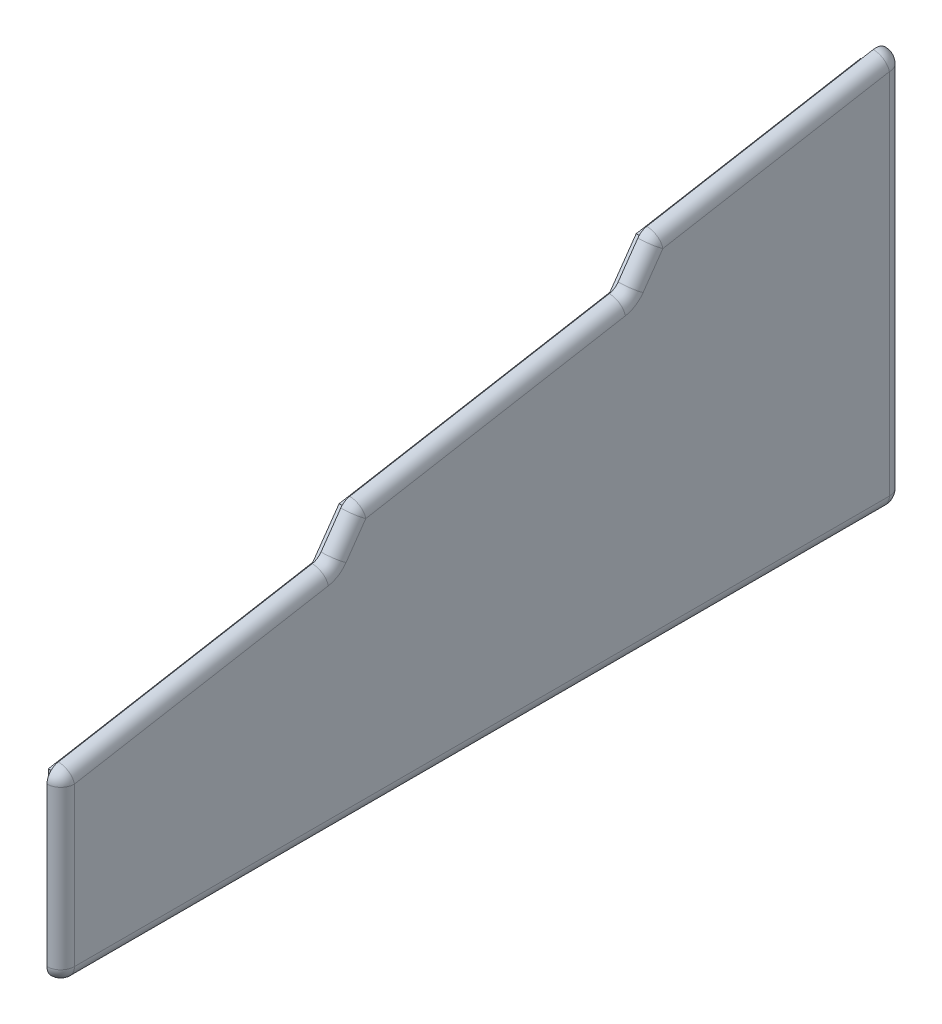
SolidWorks part; units mm, degrees
ref_plane "Front Plane" through (0, 0, 0) normal (0, 0, 1) x (1, 0, 0)
ref_plane "Top Plane" through (0, 0, 0) normal (0, 1, 0) x (1, 0, 0)
ref_plane "Right Plane" through (0, 0, 0) normal (1, 0, 0) x (0, 0, -1)
sketch "Sketch1" plane through (-376.4232, 0, 0) normal (-1, 0, 0) x (0, 0, 1)
  line L0 (-26.7829, -11.088) -> (-26.7829, -4.088) construction
  line L2 (-33.3829, -4.088) -> (-33.3829, -11.088) construction
  line L3 (-30.3829, -14.088) -> (147.43, -14.088) construction
  line L4 (150.43, -11.088) -> (150.43, -4.088) construction
  line L6 (143.83, -4.088) -> (143.83, -11.088) construction
  line L7 (143.83, -11.088) -> (-26.7829, -11.088) construction
  line L8 (19.5578, 63.3486) -> (-29.8619, 72.0626) construction
  line L9 (-33.3829, 69.1082) -> (-33.3829, -4.088) construction
  line L11 (-26.7829, -4.088) -> (-26.7829, 9.512) construction
  line L12 (-26.7829, 9.512) -> (-30.3829, 13.112) construction
  line L13 (-30.3829, 13.112) -> (-30.3829, 69.1082) construction
  line L14 (-30.3829, 69.1082) -> (19.0368, 60.3942) construction
  line L15 (19.0368, 60.3942) -> (24.7726, 52.2027) construction
  line L16 (24.7726, 52.2027) -> (83.8611, 41.7838) construction
  line L17 (83.8611, 41.7838) -> (89.5968, 33.5922) construction
  line L18 (89.5968, 33.5922) -> (147.43, 23.3947) construction
  line L19 (147.43, 23.3947) -> (147.43, 13.112) construction
  line L20 (147.43, 13.112) -> (143.83, 9.512) construction
  line L21 (143.83, 9.512) -> (143.83, -4.088) construction
  line L23 (150.43, -4.088) -> (150.43, 23.3947) construction
  line L24 (147.9509, 26.3491) -> (92.5653, 36.1151) construction
  line L25 (90.6288, 37.3488) -> (86.3185, 43.5045) construction
  line L26 (84.382, 44.7382) -> (27.7411, 54.7255) construction
  line L27 (25.8046, 55.9592) -> (21.4943, 62.1149) construction
  line L28 (-26.7829, -11.088) -> (-26.7829, -4.088)
  line L30 (-33.3829, -4.088) -> (-33.3829, -11.088)
  line L31 (-30.3829, -14.088) -> (147.43, -14.088)
  line L32 (150.43, -11.088) -> (150.43, -4.088)
  line L34 (143.83, -4.088) -> (143.83, -11.088)
  line L35 (143.83, -11.088) -> (-26.7829, -11.088)
  line L36 (19.5578, 63.3486) -> (-29.8619, 72.0626)
  line L37 (-33.3829, 69.1082) -> (-33.3829, -4.088)
  line L39 (-26.7829, -4.088) -> (-26.7829, 9.512)
  line L40 (-26.7829, 9.512) -> (-30.3829, 13.112)
  line L41 (-30.3829, 13.112) -> (-30.3829, 69.1082)
  line L42 (-30.3829, 69.1082) -> (19.0368, 60.3942)
  line L43 (19.0368, 60.3942) -> (24.7726, 52.2027)
  line L44 (24.7726, 52.2027) -> (83.8611, 41.7838)
  line L45 (83.8611, 41.7838) -> (89.5968, 33.5922)
  line L46 (89.5968, 33.5922) -> (147.43, 23.3947)
  line L47 (147.43, 23.3947) -> (147.43, 13.112)
  line L48 (147.43, 13.112) -> (143.83, 9.512)
  line L49 (143.83, 9.512) -> (143.83, -4.088)
  line L51 (150.43, -4.088) -> (150.43, 23.3947)
  line L52 (147.9509, 26.3491) -> (92.5653, 36.1151)
  line L53 (90.6288, 37.3488) -> (86.3185, 43.5045)
  line L54 (84.382, 44.7382) -> (27.7411, 54.7255)
  line L55 (25.8046, 55.9592) -> (21.4943, 62.1149)
  arc A0 (-33.3829, -11.088) -> (-30.3829, -14.088) centre (-30.3829, -11.088) ccw construction
  arc A1 (147.43, -14.088) -> (150.43, -11.088) centre (147.43, -11.088) ccw construction
  arc A2 (-29.8619, 72.0626) -> (-33.3829, 69.1082) centre (-30.3829, 69.1082) ccw construction
  arc A3 (150.43, 23.3947) -> (147.9509, 26.3491) centre (147.43, 23.3947) ccw construction
  arc A4 (90.6288, 37.3488) -> (92.5653, 36.1151) centre (93.0862, 39.0695) ccw construction
  arc A5 (86.3185, 43.5045) -> (84.382, 44.7382) centre (83.8611, 41.7838) ccw construction
  arc A6 (25.8046, 55.9592) -> (27.7411, 54.7255) centre (28.262, 57.6799) ccw construction
  arc A7 (21.4943, 62.1149) -> (19.5578, 63.3486) centre (19.0368, 60.3942) ccw construction
  arc A8 (-33.3829, -11.088) -> (-30.3829, -14.088) centre (-30.3829, -11.088) ccw
  arc A9 (147.43, -14.088) -> (150.43, -11.088) centre (147.43, -11.088) ccw
  arc A10 (-29.8619, 72.0626) -> (-33.3829, 69.1082) centre (-30.3829, 69.1082) ccw
  arc A11 (150.43, 23.3947) -> (147.9509, 26.3491) centre (147.43, 23.3947) ccw
  arc A12 (90.6288, 37.3488) -> (92.5653, 36.1151) centre (93.0862, 39.0695) ccw
  arc A13 (86.3185, 43.5045) -> (84.382, 44.7382) centre (83.8611, 41.7838) ccw
  arc A14 (25.8046, 55.9592) -> (27.7411, 54.7255) centre (28.262, 57.6799) ccw
  arc A15 (21.4943, 62.1149) -> (19.5578, 63.3486) centre (19.0368, 60.3942) ccw
extrude "Boss-Extrude1" add sketch "Sketch1" along normal blind 3 contours L37 L30 A8 L31 A9 L32 L51 A11 L52 A12 L53 A13 L54 A14 L55 A15 L36 A10
fillet "Fillet1" radius 3 16 edges at (-379.4232, 67.7056, -5.1521) (-379.4232, 62.9243, 20.6487) (-379.4232, 59.0371, 23.6494) (-379.4232, 55.1498, 26.6501) (-379.4232, 49.7318, 56.0615) (-379.4232, 44.3139, 85.473) (-379.4232, 40.4266, 88.4736) (-379.4232, 36.5393, 91.4743) (-379.4232, 31.2321, 120.2581) (-379.4232, 25.3231, 149.7281) (-379.4232, 6.1533, 150.43) (-379.4232, -13.2093, 149.5513) (-379.4232, -14.088, 58.5236) (-379.4232, -13.2093, -32.5042) (-379.4232, 29.0101, -33.3829) (-379.4232, 71.4063, -32.3113)
sketch "Sketch2" plane through (-376.4232, 0, 0) normal (1, 0, 0) x (0, 0, -1)
  line L28 (-147.13, 13.2363) -> (-143.53, 9.6363)
  line L29 (-147.13, 23.143) -> (-147.13, 13.2363)
  line L30 (-89.4224, 33.3184) -> (-147.13, 23.143)
  line L31 (-83.6866, 41.5099) -> (-89.4224, 33.3184)
  line L32 (-24.5981, 51.9288) -> (-83.6866, 41.5099)
  line L33 (-18.8624, 60.1203) -> (-24.5981, 51.9288)
  line L34 (30.0829, 68.7507) -> (-18.8624, 60.1203)
  line L35 (30.0829, 13.2363) -> (30.0829, 68.7507)
  line L36 (26.4829, 9.6363) -> (30.0829, 13.2363)
  line L37 (26.4829, -4.088) -> (26.4829, 9.6363)
  line L38 (26.4829, -10.788) -> (26.4829, -4.088)
  line L39 (-143.53, -10.788) -> (26.4829, -10.788)
  line L40 (-143.53, -4.088) -> (-143.53, -10.788)
  line L41 (-143.53, 9.6363) -> (-143.53, -4.088)
  line L42 (-147.13, 13.2363) -> (-143.53, 9.6363)
  line L43 (-147.13, 23.143) -> (-147.13, 13.2363)
  line L44 (-89.4224, 33.3184) -> (-147.13, 23.143)
  line L45 (-83.6866, 41.5099) -> (-89.4224, 33.3184)
  line L46 (-24.5981, 51.9288) -> (-83.6866, 41.5099)
  line L47 (-18.8624, 60.1203) -> (-24.5981, 51.9288)
  line L48 (30.0829, 68.7507) -> (-18.8624, 60.1203)
  line L49 (30.0829, 13.2363) -> (30.0829, 68.7507)
  line L50 (26.4829, 9.6363) -> (30.0829, 13.2363)
  line L51 (26.4829, -4.088) -> (26.4829, 9.6363)
  line L52 (26.4829, -10.788) -> (26.4829, -4.088)
  line L53 (-143.53, -10.788) -> (26.4829, -10.788)
  line L54 (-143.53, -4.088) -> (-143.53, -10.788)
  line L55 (-143.53, 9.6363) -> (-143.53, -4.088)
  dimension "D1" = 0.3
extrude "Boss-Extrude2" add sketch "Sketch2" along normal blind 3 contours L53 L50 L49 L48 L47 L46 L45 L44 L43 L42 region at (-376.4232, 19.5743, 45.2549)
sketch "Sketch3" plane through (0, -10.788, 0) normal (0, -1, 0) x (1, 0, 0)
  line L0 (-373.4232, 143.53) -> (-373.4232, -26.4829) construction
  line L1 (-376.4232, 143.83) -> (-373.4232, 143.83)
  line L2 (-373.4232, 143.83) -> (-373.4232, 140.2803)
  line L3 (-376.4232, 143.53) -> (-376.4232, -26.4829) construction
  line L4 (-376.4232, -26.7829) -> (-373.4232, -26.7829)
  line L5 (-373.4232, -26.7829) -> (-373.4232, -23.2332)
  line L6 (-376.4232, 143.83) -> (-376.4232, -26.7829) construction
  line L7 (-376.4232, 143.83) -> (-376.4232, 142.33)
  line L8 (-376.4232, -26.7829) -> (-376.4232, -25.2829)
  line L9 (-373.4232, -22.9293) -> (-373.4232, -23.2332)
  line L11 (-373.4232, 140.2803) -> (-373.4232, 139.9764)
  arc A0 (-376.4232, 143.83) -> (-373.4232, 140.2803) centre (-372.8232, 143.83) ccw
  arc A1 (-376.4232, 143.83) -> (-370.0135, 141.5792) centre (-372.8232, 143.83) ccw construction
  arc A2 (-373.4232, -23.2332) -> (-376.4232, -26.7829) centre (-372.8232, -26.7829) ccw
  arc A3 (-370.0135, -24.5321) -> (-376.4232, -26.7829) centre (-372.8232, -26.7829) ccw construction
  arc A4 (-376.7232, 143.83) -> (-373.4732, 139.9845) centre (-372.8232, 143.83) ccw
  arc A5 (-373.4732, -22.9374) -> (-376.7232, -26.7829) centre (-372.8232, -26.7829) ccw
  arc A6 (-373.4732, -22.9374) -> (-373.4232, -22.9293) centre (-372.8232, -26.7829) cw
  arc A7 (-373.4732, 139.9845) -> (-373.4232, 139.9764) centre (-372.8232, 143.83) ccw
  line M4 (-376.4232, 143.53) -> (-376.4232, -26.4829)
  line M5 (-376.4232, -26.4829) -> (-373.4232, -26.4829)
  line M6 (-373.4232, -26.4829) -> (-373.4232, 143.53)
  line M7 (-373.4232, 143.53) -> (-376.4232, 143.53)
  dimension "D1" = 0.3
extrude "Cut-Extrude1" cut sketch "Sketch3" against normal up to surface and the other way through all contours A0 M7 M6 | A4 A7 A0 M6 M7 M4 region at (-376.4169, -10.788, 143.4835) region at (-374.6497, -10.788, 142.2079) up to face at (-374.9232, 11.4363, 145.33)
extrude "Cut-Extrude2" cut sketch "Sketch3<3>" against normal up to surface (20.4243 mm away) contours A2 M6 M5 | A6 A5 A2 M4 M5 M6 region at (-375.2214, -10.788, -23.7666) region at (-374.6497, -10.788, -25.1608) up to face at (-374.9232, 11.4363, -28.2829)
sketch "Sketch3<3>" plane through (0, -10.788, 0) normal (0, -1, 0) x (1, 0, 0) same geometry as "Sketch3"
mirror "Mirror1" about plane through (-373.4232, 0, 0) normal (1, 0, 0) of bodies 104
delete or keep bodies "Body-Delete/Keep 1" type delete bodies bodies 104
delete or keep bodies "Body-Delete/Keep 2" [suppressed] type delete bodies bodies 105
